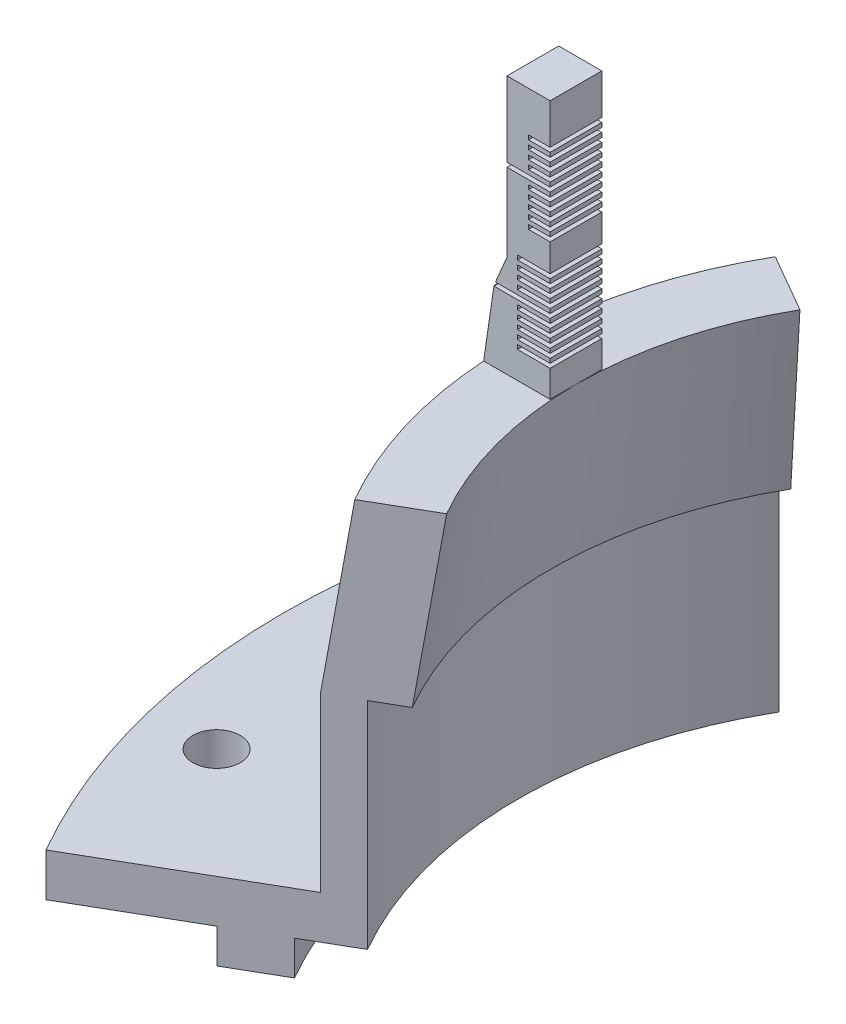
SolidWorks part; units mm, degrees
ref_plane "Front Plane" through (0, 0, 0) normal (0, 0, 1) x (1, 0, 0)
ref_plane "Top Plane" through (0, 0, 0) normal (0, 1, 0) x (1, 0, 0)
ref_plane "Right Plane" through (0, 0, 0) normal (1, 0, 0) x (0, 0, -1)
sketch "Sketch1" plane through (0, 0, 0) normal (0, 0, 1) x (1, 0, 0)
  line L1 (-5, 10) -> (5, 10)
  line L2 (-5, 10) -> (-5, 0)
  line L3 (-5, 0) -> (5, 0)
  line L4 (5, 10) -> (5, 0)
  dimension "D1" = 10
  dimension "D2" = 10
extrude "Boss-Extrude1" [suppressed] add sketch "Sketch1" against normal blind 10 draft 15 contours L4 L3 L2 L1
sketch "Sketch2" plane through (0, 0, 0) normal (0, 0, 1) x (1, 0, 0)
  line L0 (0, 0) -> (0, 29.4965) construction
sketch "Sketch3" plane through (0, 0, 0) normal (0, 1, 0) x (1, 0, 0)
  circle A0 centre (0, 0) radius 45 construction
  dimension "D1" = 90
sketch "Sketch7" plane through (0, 0, 0) normal (0, 0, 1) x (1, 0, 0)
  line L0 (-75, 8) -> (-60.5, 8)
  line L1 (-60.5, 8) -> (-60.5, 4)
  line L2 (-60.5, 4) -> (-53.9, 4)
  line L3 (-53.9, 4) -> (-53.9, 8)
  line L4 (-53.9, 8) -> (-47.7, 8)
  line L5 (-47.7, 8) -> (-47.7, 18)
  line L6 (-47.7, 18) -> (-47.7, 33)
  line L8 (-40.9823, 53) -> (-48.7823, 53)
  line L10 (-51.7, 13) -> (-75, 13)
  line L11 (-75, 13) -> (-75, 8)
  line L12 (0, -200000) -> (0, 200029.4965) construction
  line L13 (-47.7, 33) -> (-43.9, 33)
  line L14 (-43.9, 33) -> (-40.9823, 53)
  line L15 (-48.7823, 53) -> (-51.7, 33)
  line L16 (-51.7, 33) -> (-51.7, 13)
  dimension "D1" = 53.9
  dimension "D2" = 6.6
  dimension "D3" = 4
  dimension "D4" = 4
  dimension "D5" = 75
  dimension "D6" = 5
  dimension "D7" = 6.2
  dimension "D8" = 90
  dimension "D9" = 10
  dimension "D10" = 15
  dimension "D11" = 20
  dimension "D13" = 3.8
  dimension "D14" = 4
  dimension "D15" = 98.3
revolve "back" add sketch "Sketch7" angle 30 about L0
sketch "Sketch9" plane through (0, 8, 0) normal (0, -1, 0) x (-1, 0, 0)
  line L0 (0, 0) -> (65.2, 17.4703) construction
  line L1 (65.2, 17.4703) -> (65.2, 14.7203) construction
  line L2 (65.2, -17.4703) -> (0, 0) construction
  line L3 (65.2, -14.7203) -> (65.2, -17.4703) construction
  line L4 (83.6224, 0) -> (170.0314, 0) construction
  circle A0 centre (65.2, 17.4703) radius 2.75
  circle A1 centre (65.2, -17.4703) radius 2.75
  dimension "D1" = 5.5
  dimension "D2" = 5.5
  dimension "D3" = 67.5
  dimension "D4" = 67.5
  dimension "D5" = 15
sketch "Sketch10" plane through (0, 0, 0) normal (0, 0, 1) x (1, 0, 0)
  line L0 (-40.9823, 53) -> (-40.9823, 83)
  line L1 (-40.9823, 83) -> (-45.9823, 83)
  line L2 (-45.9823, 83) -> (-45.9823, 53)
  line L4 (-35.4917, 53) -> (-42.2467, 53) construction
  line L5 (-45.9823, 53) -> (-40.9823, 53)
  dimension "D1" = 5
  dimension "D2" = 90
  dimension "D3" = 30
revolve "top ruler" [suppressed] add sketch "Sketch10" angle 3 about L0
extrude "screw hole" cut sketch "Sketch9" against normal through all
sketch "Sketch13" plane through (0, 53, 0) normal (0, 1, 0) x (1, 0, 0)
  line L0 (0, 0) -> (-40.9823, 0) construction
  line L2 (-40.9823, -3) -> (-45.9823, -3)
  line L3 (-40.9823, -3) -> (-40.9823, 3)
  line L4 (-40.9823, 3) -> (-45.9823, 3)
  line L5 (-45.9823, -3) -> (-45.9823, 3)
  arc A0 (-35.4917, 20.4912) -> (-35.4917, -20.4912) centre (0, 0) ccw construction
  dimension "D1" = 5
  dimension "D2" = 6
extrude "Boss-Extrude2" add sketch "Sketch13" along normal blind 30
sketch "Sketch14" plane through (-45.9823, 0, 0) normal (-1, 0, 0) x (0, 0, 1)
  line L0 (3, 68) -> (6.996, 53)
  line L1 (3, 83) -> (3, 53) construction
  line L5 (6.996, 53) -> (3, 53)
rib "Rib1" [suppressed] sketch "Sketch14" sketch "Sketch14" thickness 5 extrusion direction parallel to sketch draft on no parameters "D1"=5
chamfer "Chamfer1" distance 5 angle 67 1 edges at (-45.9823, 53, 0) first distance on face at (-42.0604, 53, 0)
sketch "Sketch15" plane through (0, 0, 3) normal (0, 0, 1) x (1, 0, 0)
  line L0 (-40.4035, 61.1207) -> (-47.503, 61.1207)
  line L2 (39.3937, 61.1207) -> (-39.3937, 61.1207) construction
  line L3 (-40.5384, 73.8207) -> (-45.9823, 73.8207)
  line L5 (-45.9823, 83) -> (-45.9823, 64.7793) construction
  line L6 (17.4269, 73.8207) -> (-39.22, 73.8207) construction
  parabola Q0 (-48.69, 53) -> (-47.486, 61.2367) focus (307907.5362, -44959.4806) apex (-49.0549, 50.5031) construction
extrude "long" cut sketch "Sketch15" against normal through all thin thin type one direction wall 0.5
sketch "Sketch16" plane through (0, 0, 3) normal (0, 0, 1) x (1, 0, 0)
  line L0 (-40.2559, 72.8207) -> (-43.4825, 72.8207)
  line L2 (-45.9823, 73.8207) -> (-40.9823, 73.8207) construction
  dimension "D1" = 1
extrude "short 1" cut sketch "Sketch16" against normal through all thin thin type one direction wall 0.5
pattern_linear "LPattern1" count 6 spacing 1 along (0, 1, 0) count 5 spacing 1 along (0, -1, 0) of "short 1"
sketch "Sketch17" plane through (0, 0, 3) normal (0, 0, 1) x (1, 0, 0)
  line L0 (-40.9823, 60.1207) -> (-44.7667, 60.1207)
  line L1 (-40.9823, 61.1207) -> (-40.9823, 53) construction
  line L2 (-40.9823, 61.1207) -> (-47.503, 61.1207) construction
  dimension "D1" = 1
extrude "short 2" cut sketch "Sketch17" against normal through all thin thin type one direction wall 0.5
ref_plane "Plane1" through (-40.9823, 68.8207, 3) normal (0, -1, 0) x (-1, 0, 0)
pattern_linear "LPattern2" count 6 spacing 1 along (0, 1, 0) count 5 spacing 1 along (0, -1, 0) of "short 2"
sketch "Sketch19" plane through (0, 83, 0) normal (0, 1, 0) x (1, 0, 0)
  line L0 (-40.9823, 3) -> (-45.9823, 3) construction
  line L1 (-41.9823, 2) -> (-44.9823, 2)
  line L2 (-41.9823, 2) -> (-41.9823, -2)
  line L3 (-41.9823, -2) -> (-44.9823, -2)
  line L4 (-44.9823, 2) -> (-44.9823, -2)
  line L5 (-45.9823, -3) -> (-40.9823, -3) construction
  line L6 (-45.9823, 3) -> (-45.9823, -3) construction
  line L7 (-40.9823, -3) -> (-40.9823, 3) construction
  dimension "D1" = 1
  dimension "D2" = 1
  dimension "D3" = 1
  dimension "D4" = 1
extrude "Boss-Extrude3" add sketch "Sketch19" against normal up to surface (30 mm away) up to face at (-42.1966, 53, 10.3235)
